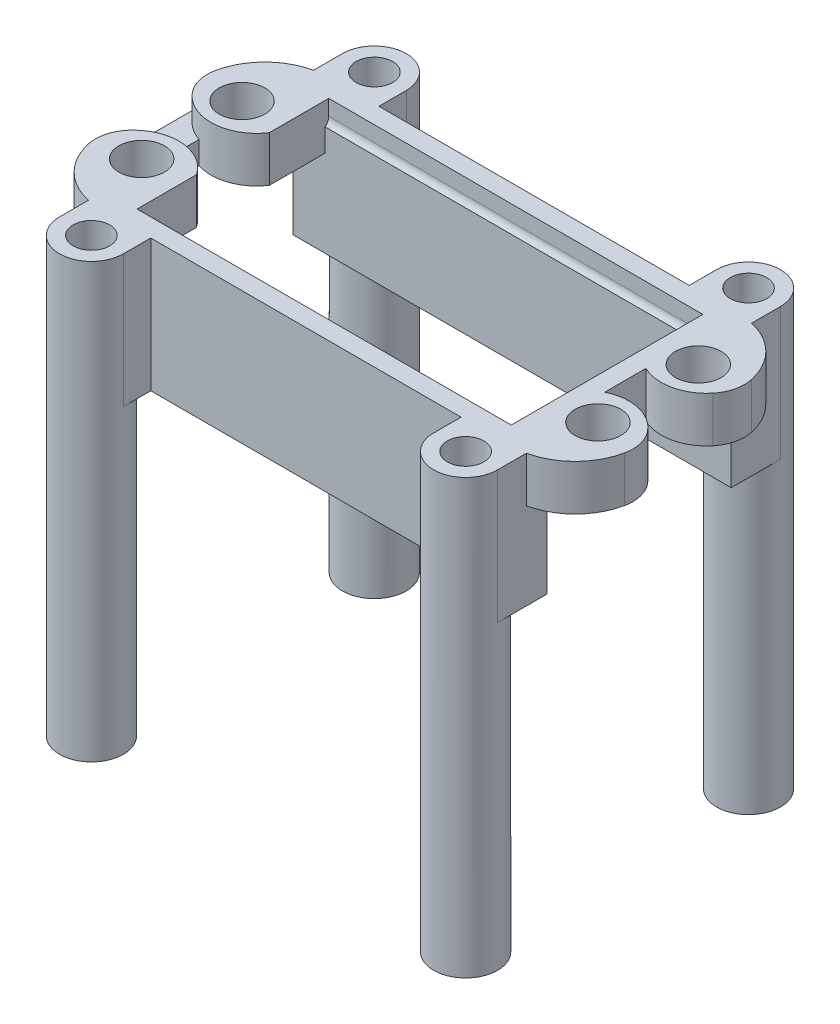
SolidWorks part; units mm, degrees
ref_plane "Front Plane" through (0, 0, 0) normal (0, 0, 1) x (1, 0, 0)
ref_plane "Top Plane" through (0, 0, 0) normal (0, 1, 0) x (1, 0, 0)
ref_plane "Right Plane" through (0, 0, 0) normal (1, 0, 0) x (0, 0, -1)
sketch "Sketch1" plane through (0, 0, 0) normal (0, 1, 0) x (1, 0, 0)
  line L0 (-20, 0) -> (-22, 0) construction
  line L1 (20.5, 10.5) -> (-20.5, 10.5)
  line L2 (20.5, 10.5) -> (20.5, -10.5)
  line L3 (20.5, -10.5) -> (-20.5, -10.5)
  line L4 (-20.5, 10.5) -> (-20.5, 4)
  line L5 (20.5, 10.5) -> (-20.5, -10.5) construction
  line L6 (20.5, -10.5) -> (-20.5, 10.5) construction
  line L7 (22.5, 12.5) -> (-22.5, 12.5)
  line L8 (22.5, 2.2557) -> (22.5, -2.2557)
  line L9 (22.5, -12.5) -> (-22.5, -12.5)
  line L11 (22.5, 12.5) -> (-22.5, -12.5) construction
  line L12 (22.5, -12.5) -> (-22.5, 12.5) construction
  line L16 (-20.5, -4) -> (-20.5, -10.5)
  line L17 (0, 0) -> (-37.8746, 0) construction
  line L18 (0, 0) -> (0, 8.5057) construction
  circle A0 centre (-25, 5.5) radius 2.5
  circle A1 centre (-25, -5.5) radius 2.5
  arc A4 (-22.5, 12.5) -> (-29.3504, 6.9605) centre (-22.5, 5.4945) ccw
  arc A5 (-20.5, 4) -> (-28.5206, 3.5732) centre (-24.6686, 6.761) cw
  arc A6 (-20.5, -4) -> (-28.5206, -3.5732) centre (-24.6686, -6.761) ccw
  arc A7 (-22.5, -12.5) -> (-29.3504, -6.9605) centre (-22.5, -5.4945) cw
  arc A8 (22.5, -12.5) -> (29.3504, -6.9605) centre (22.5, -5.4945) ccw
  circle A9 centre (25, -5.5) radius 2.5
  arc A10 (22.5, -2.2557) -> (28.5206, -3.5732) centre (24.6686, -6.761) cw
  circle A11 centre (25, 5.5) radius 2.5
  arc A12 (22.5, 2.2557) -> (28.5206, 3.5732) centre (24.6686, 6.761) ccw
  arc A13 (22.5, 12.5) -> (29.3504, 6.9605) centre (22.5, 5.4945) cw
  arc A14 (29.3504, -6.9605) -> (28.5206, -3.5732) centre (25.439, -6.1234) ccw
  arc A15 (28.5206, 3.5732) -> (29.3504, 6.9605) centre (25.439, 6.1234) ccw
  arc A16 (-28.5206, -3.5732) -> (-29.3504, -6.9605) centre (-25.439, -6.1234) ccw
  arc A17 (-29.3504, 6.9605) -> (-28.5206, 3.5732) centre (-25.439, 6.1234) ccw
  point P0 (0, 0)
  point P6 (0, 0)
  point P13 (-21, 0)
  point P36 (29.5055, -5.4945)
  point P46 (29.5055, 5.4945)
  point P49 (-29.5055, -5.4945)
  point P52 (-29.5055, 5.4945)
  dimension "D6" = 5
  dimension "D8" = 4.5
  dimension "D9" = 11
  dimension "D10" = 5
  dimension "D5" = 4
  dimension "D2" = 2
  dimension "D3" = 41
  dimension "D4" = 21
extrude "Boss-Extrude1" add sketch "Sketch1" along normal blind 2.5
sketch "Sketch4" plane through (0, 0, 0) normal (0, 1, 0) x (1, 0, 0)
  line L0 (-20.5, -10.5) -> (-20.5, -12.5) construction
  line L1 (-20.5, 10.5) -> (-20.5, 12.5) construction
  line L2 (22.5, 12.5) -> (-22.5, 12.5) construction
  line L3 (-20.5, 12.5) -> (-20.5, 15.5) construction
  line L4 (0, 0) -> (-12.5316, 0) construction
  line L5 (-22.5, -12.5) -> (22.5, -12.5) construction
  line L6 (-20.5, -12.5) -> (-20.5, -15.5) construction
  circle A0 centre (-20.5, 15.5) radius 2
  circle A1 centre (-20.5, 15.5) radius 3.5
  circle A2 centre (20.5, 15.5) radius 2
  circle A3 centre (20.5, 15.5) radius 3.5
  circle A4 centre (-20.5, -15.5) radius 2
  circle A5 centre (-20.5, -15.5) radius 3.5
  circle A6 centre (20.5, -15.5) radius 2
  circle A7 centre (20.5, -15.5) radius 3.5
  dimension "D1" = 1.5
  dimension "D2" = 4
  dimension "D3" = 1.5
  dimension "D4" = 4
  dimension "D8" = 4
  dimension "D9" = 1.5
  dimension "D10" = 1.5
  dimension "D11" = 4
  dimension "D5" = 41
  dimension "D6" = 3
  dimension "D7" = 41
  dimension "D12" = 3
extrude "Boss-Extrude2" add sketch "Sketch4" along normal up to surface (2.5 mm away) and the other way blind 45 up to face at (0.2335, 2.5, 0)
sketch "Sketch5" plane through (0, 0, 0) normal (0, 1, 0) x (1, 0, 0)
  line L1 (-26.2086, 2.0041) -> (-26.2086, -2.0041)
  line L2 (-29.3241, 5.1717) -> (-29.3241, -5.1717)
  line L29 (-17, 15.5) -> (-17, 12.5)
  line L30 (-17, -15.5) -> (-18.5, -15.5)
  line L31 (-24, -15.5) -> (-24, -12.3375)
  line L32 (-24, 12.3375) -> (-24, 15.5)
  line L33 (-24, 15.5) -> (-22.5, 15.5)
  line L34 (-18.5, 15.5) -> (-17, 15.5)
  line L35 (-22.5, -15.5) -> (-24, -15.5)
  line L36 (-18.6972, -12.5) -> (18.6972, -12.5)
  line L37 (-22.5, -12.5) -> (-22.3028, -12.5)
  line L38 (-20.5, -10.5) -> (-20.5, -4)
  line L39 (20.5, -10.5) -> (-20.5, -10.5)
  line L40 (20.5, 10.5) -> (20.5, -10.5)
  line L41 (-20.5, 10.5) -> (20.5, 10.5)
  line L42 (-20.5, 4) -> (-20.5, 10.5)
  line L43 (-22.3028, 12.5) -> (-22.5, 12.5)
  line L44 (18.6972, 12.5) -> (-18.6972, 12.5)
  line L45 (22.5, 12.5) -> (22.3028, 12.5)
  line L46 (22.5, -2.2557) -> (22.5, 2.2557)
  line L47 (22.3028, -12.5) -> (22.5, -12.5)
  line L48 (-17, -12.5) -> (17, -12.5)
  line L50 (-20.5, -10.5) -> (-20.5, -4)
  line L51 (20.5, -10.5) -> (-20.5, -10.5)
  line L52 (20.5, 10.5) -> (20.5, -10.5)
  line L53 (-20.5, 10.5) -> (20.5, 10.5)
  line L54 (-20.5, 4) -> (-20.5, 10.5)
  line L56 (17, 12.5) -> (-17, 12.5)
  line L58 (22.5, -2.2557) -> (22.5, 2.2557)
  line L60 (17, 15.5) -> (18.5, 15.5)
  line L61 (24, 15.5) -> (24, 12.3375)
  line L62 (24, -15.5) -> (22.5, -15.5)
  line L63 (17, -15.5) -> (17, -12.5)
  line L64 (22.5, 15.5) -> (24, 15.5)
  line L65 (18.5, -15.5) -> (17, -15.5)
  line L66 (24, -12.3375) -> (24, -15.5)
  line L67 (-17, -12.5) -> (-17, -15.5)
  line L68 (17, 12.5) -> (17, 15.5)
  arc A32 (-18.6972, 12.5) -> (-22.3028, 12.5) centre (-20.5, 15.5) ccw construction
  arc A33 (-22.3028, -12.5) -> (-18.6972, -12.5) centre (-20.5, -15.5) ccw construction
  arc A34 (-18.5, -15.5) -> (-22.5, -15.5) centre (-20.5, -15.5) ccw
  arc A35 (-22.5, 15.5) -> (-18.5, 15.5) centre (-20.5, 15.5) ccw
  circle A36 centre (-25, 5.5) radius 2.5
  circle A37 centre (-25, -5.5) radius 2.5
  circle A38 centre (25, -5.5) radius 2.5
  circle A39 centre (25, 5.5) radius 2.5
  arc A40 (22.5, -15.5) -> (18.5, -15.5) centre (20.5, -15.5) ccw
  arc A41 (18.5, 15.5) -> (22.5, 15.5) centre (20.5, 15.5) ccw
  arc A42 (22.3028, 12.5) -> (18.6972, 12.5) centre (20.5, 15.5) ccw construction
  arc A43 (18.6972, -12.5) -> (22.3028, -12.5) centre (20.5, -15.5) ccw construction
  arc A48 (22.3028, -12.5) -> (18.6972, -12.5) centre (20.5, -15.5) ccw
  arc A49 (-18.6972, -12.5) -> (-22.3028, -12.5) centre (-20.5, -15.5) ccw
  arc A50 (-29.3504, -6.9605) -> (-22.5, -12.5) centre (-22.5, -5.4945) ccw
  arc A51 (-28.5206, -3.5732) -> (-29.3504, -6.9605) centre (-25.439, -6.1234) ccw
  arc A52 (-20.5, -4) -> (-28.5206, -3.5732) centre (-24.6686, -6.761) ccw
  arc A53 (-28.5206, 3.5732) -> (-20.5, 4) centre (-24.6686, 6.761) ccw
  arc A54 (-29.3504, 6.9605) -> (-28.5206, 3.5732) centre (-25.439, 6.1234) ccw
  arc A55 (-22.5, 12.5) -> (-29.3504, 6.9605) centre (-22.5, 5.4945) ccw
  arc A56 (-22.3028, 12.5) -> (-18.6972, 12.5) centre (-20.5, 15.5) ccw
  arc A57 (18.6972, 12.5) -> (22.3028, 12.5) centre (20.5, 15.5) ccw
  arc A58 (29.3504, 6.9605) -> (22.5, 12.5) centre (22.5, 5.4945) ccw
  arc A59 (28.5206, 3.5732) -> (29.3504, 6.9605) centre (25.439, 6.1234) ccw
  arc A60 (22.5, 2.2557) -> (28.5206, 3.5732) centre (24.6686, 6.761) ccw
  arc A61 (28.5206, -3.5732) -> (22.5, -2.2557) centre (24.6686, -6.761) ccw
  arc A62 (29.3504, -6.9605) -> (28.5206, -3.5732) centre (25.439, -6.1234) ccw
  arc A63 (22.5, -12.5) -> (29.3504, -6.9605) centre (22.5, -5.4945) ccw
  arc A66 (-29.3504, -6.9605) -> (-24, -12.3375) centre (-22.5, -5.4945) ccw
  arc A67 (-29.3241, -5.1717) -> (-29.3504, -6.9605) centre (-25.439, -6.1234) ccw
  arc A68 (-20.5, -4) -> (-26.2086, -2.0041) centre (-24.6686, -6.761) ccw
  arc A69 (-26.2086, 2.0041) -> (-20.5, 4) centre (-24.6686, 6.761) ccw
  arc A70 (-29.3504, 6.9605) -> (-29.3241, 5.1717) centre (-25.439, 6.1234) ccw
  arc A71 (-24, 12.3375) -> (-29.3504, 6.9605) centre (-22.5, 5.4945) ccw
  arc A74 (29.3504, 6.9605) -> (24, 12.3375) centre (22.5, 5.4945) ccw
  arc A75 (28.5206, 3.5732) -> (29.3504, 6.9605) centre (25.439, 6.1234) ccw
  arc A76 (22.5, 2.2557) -> (28.5206, 3.5732) centre (24.6686, 6.761) ccw
  arc A77 (28.5206, -3.5732) -> (22.5, -2.2557) centre (24.6686, -6.761) ccw
  arc A78 (29.3504, -6.9605) -> (28.5206, -3.5732) centre (25.439, -6.1234) ccw
  arc A79 (24, -12.3375) -> (29.3504, -6.9605) centre (22.5, -5.4945) ccw
  dimension "D1" = 0
extrude "Boss-Extrude3" add sketch "Sketch5" against normal blind 2.5
sketch "Sketch6" plane through (0, 0, 0) normal (0, 1, 0) x (1, 0, 0)
  line L7 (-24, 15.5) -> (-22.5, 15.5)
  line L12 (-17, 15.5) -> (-17, 12.5)
  line L13 (-17, 12.5) -> (17, 12.5)
  line L14 (17, 12.5) -> (17, 15.5)
  line L15 (17, 15.5) -> (18.5, 15.5)
  line L18 (24, 10.1) -> (-24, 10.1)
  line L21 (-18.5, 15.5) -> (-17, 15.5)
  line L22 (22.5, 15.5) -> (24, 15.5)
  line L23 (-20.5, 10.5) -> (20.5, 10.5) construction
  line L24 (-24, 10.1) -> (-24, 15.5)
  line L25 (24, 15.5) -> (24, 10.1)
  line L26 (62.5806, 0) -> (-62.5806, 0) construction
  line L27 (24, -15.5) -> (24, -10.1)
  line L28 (-24, -15.5) -> (-24, -10.1)
  line L29 (22.5, -15.5) -> (24, -15.5)
  line L30 (-18.5, -15.5) -> (-17, -15.5)
  line L31 (24, -10.1) -> (-24, -10.1)
  line L32 (17, -15.5) -> (18.5, -15.5)
  line L33 (17, -12.5) -> (17, -15.5)
  line L34 (-17, -12.5) -> (17, -12.5)
  line L35 (-17, -15.5) -> (-17, -12.5)
  line L36 (-24, -15.5) -> (-22.5, -15.5)
  arc A2 (-22.5, 15.5) -> (-18.5, 15.5) centre (-20.5, 15.5) ccw
  arc A3 (18.5, 15.5) -> (22.5, 15.5) centre (20.5, 15.5) ccw
  arc A4 (18.5, -15.5) -> (22.5, -15.5) centre (20.5, -15.5) cw
  arc A5 (-22.5, -15.5) -> (-18.5, -15.5) centre (-20.5, -15.5) cw
  point P23 (0, 0)
  dimension "D1" = 0.4
extrude "Boss-Extrude4" add sketch "Sketch6" against normal blind 12
sketch "Sketch7" plane through (0, 0, 0) normal (0, 1, 0) x (1, 0, 0)
  line L0 (-24, -15.5) -> (-24, -10.9809)
  line L1 (-17, -15.5) -> (-17, -10.9809)
  line L2 (-24, -10.9809) -> (-17, -10.9809)
  line L3 (17, -15.5) -> (17, -10.9809)
  line L4 (17, -10.9809) -> (24, -10.9809)
  line L5 (24, -10.9809) -> (24, -15.5)
  line L6 (0, 0) -> (-11.5911, 0) construction
  line L7 (24, 10.9809) -> (24, 15.5)
  line L8 (17, 10.9809) -> (24, 10.9809)
  line L9 (17, 15.5) -> (17, 10.9809)
  line L10 (-24, 10.9809) -> (-17, 10.9809)
  line L11 (-17, 15.5) -> (-17, 10.9809)
  line L12 (-24, 15.5) -> (-24, 10.9809)
  arc A2 (24, -15.5) -> (17, -15.5) centre (20.5, -15.5) ccw
  arc A3 (-17, -15.5) -> (-24, -15.5) centre (-20.5, -15.5) ccw
  arc A4 (-17, 15.5) -> (-24, 15.5) centre (-20.5, 15.5) cw
  arc A5 (24, 15.5) -> (17, 15.5) centre (20.5, 15.5) cw
extrude "Boss-Extrude5" add sketch "Sketch7" along normal up to surface (2.5 mm away) up to face at (0.1668, 2.5, 0)
fillet "Fillet2" radius 1 1 edges at (0, 0, -10.5)
fillet "Fillet3" radius 1 1 edges at (0, 0, 10.5)
